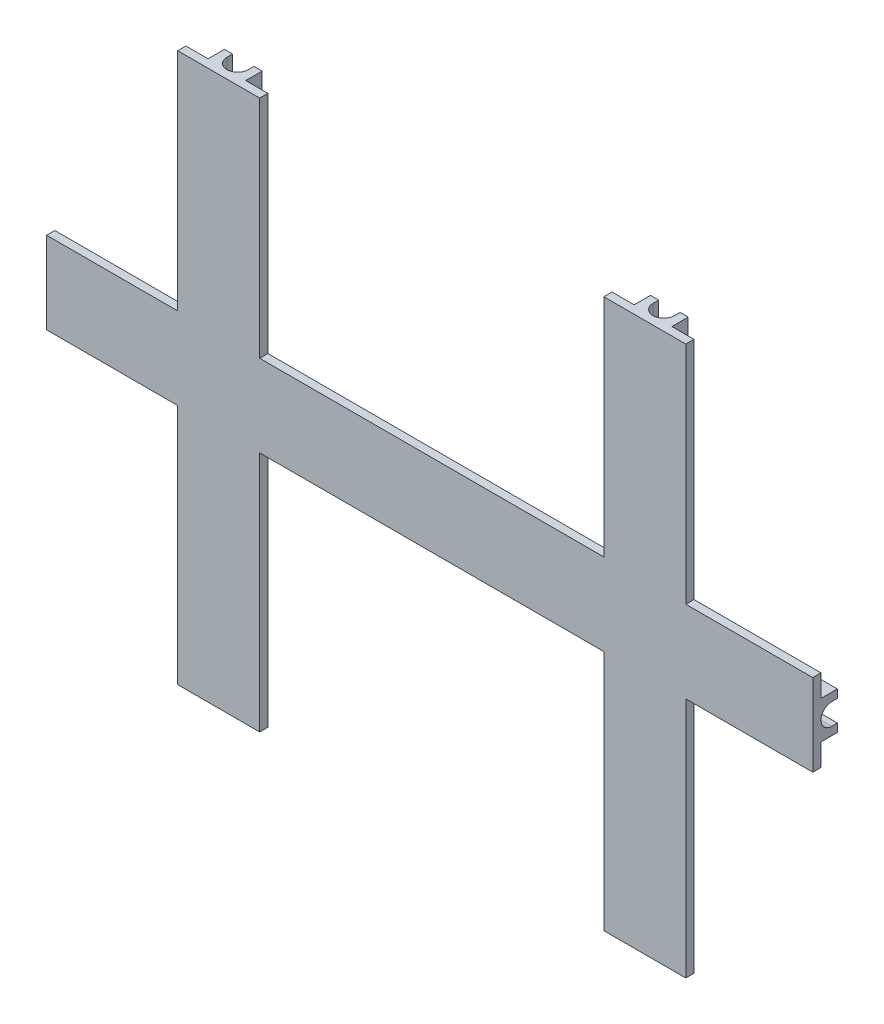
SolidWorks part; units mm, degrees
ref_plane "Спереди" through (0, 0, 0) normal (0, 0, 1) x (1, 0, 0)
ref_plane "Сверху" through (0, 0, 0) normal (0, 1, 0) x (1, 0, 0)
ref_plane "Справа" through (0, 0, 0) normal (1, 0, 0) x (0, 0, -1)
sketch "Skizze1" plane through (0, 0, 0) normal (0, 0, 1) x (1, 0, 0)
  line L0 (-31, -15.1875) -> (-31, 32.5)
  line L1 (-31, 32.5) -> (-21, 32.5)
  line L2 (-21, 32.5) -> (-21, 5)
  line L3 (-21, 5) -> (21, 5)
  line L4 (21, 5) -> (21, 32.5)
  line L5 (21, 32.5) -> (31, 32.5)
  line L6 (31, 32.5) -> (31, -34.5)
  line L7 (31, -34.5) -> (21, -34.5)
  line L8 (21, -34.5) -> (21, -5)
  line L9 (21, -5) -> (-21, -5)
  line L10 (-21, -5) -> (-21, -34.5)
  line L11 (-21, -34.5) -> (-31, -34.5)
  line L12 (-31, -34.5) -> (-31, -15.1875)
  dimension "D1" = 42
  dimension "D2" = 10
  dimension "D3" = 10
  dimension "D4" = 10
  dimension "D5" = 10
  dimension "D6" = 10
  dimension "D7" = 5
  dimension "D8" = 67
  dimension "D9" = 32.5
  dimension "D10" = 31
extrude "Aufsatz-Linear austragen1" add sketch "Skizze1" along normal blind 1
sketch "Skizze2" plane through (0, 0, 0) normal (0, 0, -1) x (-1, 0, 0)
  line L0 (31, 32.5) -> (31, -34.5) construction
  line L1 (31, 5) -> (47, 5)
  line L2 (31, 5) -> (31, -5)
  line L3 (31, -5) -> (47, -5)
  line L4 (47, 5) -> (47, -5)
  line L5 (-31, -34.5) -> (-31, 32.5) construction
  line L6 (-31, 5) -> (-46.5, 5)
  line L7 (-31, 5) -> (-31, -5)
  line L8 (-31, -5) -> (-46.5, -5)
  line L9 (-46.5, 5) -> (-46.5, -5)
  line L10 (-21, 5) -> (21, 5) construction
  dimension "D1" = 10
  dimension "D2" = 10
  dimension "D3" = 15.5
  dimension "D4" = 16
extrude "Aufsatz-Linear austragen2" add sketch "Skizze2" against normal blind 1
sketch "Skizze4" plane through (0, 0, 0) normal (0, 0, -1) x (-1, 0, 0)
  line L0 (-46.5, 5) -> (-46.5, -5) construction
  line L1 (-46.5, 2.3) -> (47, 2.3)
  line L2 (-46.5, 2.3) -> (-46.5, 1.3)
  line L3 (-46.5, 1.3) -> (47, 1.3)
  line L4 (47, 2.3) -> (47, 1.3)
  line L5 (47, -5) -> (47, 5) construction
  line L6 (-31, 32.5) -> (-21, 32.5) construction
  line L7 (-46.5, -1.3) -> (47, -1.3)
  line L8 (-46.5, -1.3) -> (-46.5, -2.3)
  line L9 (-46.5, -2.3) -> (47, -2.3)
  line L10 (47, -1.3) -> (47, -2.3)
  line L11 (-28.3, 32.5) -> (-27.3, 32.5)
  line L12 (-28.3, 32.5) -> (-28.3, -34.5)
  line L13 (-28.3, -34.5) -> (-27.3, -34.5)
  line L14 (-27.3, 32.5) -> (-27.3, -34.5)
  line L15 (-21, -34.5) -> (-31, -34.5) construction
  line L16 (31, -34.5) -> (21, -34.5) construction
  line L17 (-24.7, 32.5) -> (-23.7, 32.5)
  line L18 (-24.7, 32.5) -> (-24.7, -34.5)
  line L19 (-24.7, -34.5) -> (-23.7, -34.5)
  line L20 (-23.7, 32.5) -> (-23.7, -34.5)
  line L21 (23.7, -34.5) -> (24.7, -34.5)
  line L22 (23.7, -34.5) -> (23.7, 32.5)
  line L23 (23.7, 32.5) -> (24.7, 32.5)
  line L24 (24.7, -34.5) -> (24.7, 32.5)
  line L25 (21, 32.5) -> (31, 32.5) construction
  line L26 (-31, 5) -> (-31, 32.5) construction
  line L27 (27.3, 32.5) -> (28.3, 32.5)
  line L28 (27.3, 32.5) -> (27.3, -34.5)
  line L29 (27.3, -34.5) -> (28.3, -34.5)
  line L30 (28.3, 32.5) -> (28.3, -34.5)
  line L31 (-21, 32.5) -> (-21, 5) construction
  line L32 (21, 5) -> (21, 32.5) construction
  line L33 (31, 32.5) -> (31, 5) construction
  line L34 (47, 5) -> (31, 5) construction
  line L35 (31, -5) -> (47, -5) construction
  dimension "D1" = 2.7
  dimension "D2" = 1
  dimension "D3" = 1
  dimension "D4" = 2.7
  dimension "D5" = 1
  dimension "D6" = 2.7
  dimension "D7" = 1
  dimension "D8" = 2.7
  dimension "D9" = 1
  dimension "D10" = 2.7
  dimension "D11" = 1
  dimension "D12" = 2.7
extrude "Aufsatz-Linear austragen5" add sketch "Skizze4" along normal blind 2 contours L28 L29 L30 L27 | L24 L23 L22 L21 | L1 L4 L3 L2 | L7 L10 L9 L8 | L20 L19 L18 L17 | L14 L13 L12 L11
fillet "Verrundung1" radius 1.3 1 edges at (24.7, 17.4, 0)
fillet "Verrundung2" radius 1.3 1 edges at (27.3, 17.4, 0)
fillet "Verrundung3" radius 1.3 5 edges at (-37.65, 1.3, 0) (-26, 1.3, 0) (0, 1.3, 0) (26, 1.3, 0) (37.4, 1.3, 0)
fillet "Verrundung4" radius 1.3 5 edges at (37.4, -1.3, 0) (26, -1.3, 0) (0, -1.3, 0) (-26, -1.3, 0) (-37.65, -1.3, 0)
fillet "Verrundung5" radius 1.3 4 edges at (24.7, 2.3, -1.65) (27.3, 2.3, -1.65) (26.9192, 2.3, -0.3808) (25.0808, 2.3, -0.3808)
fillet "Verrundung6" radius 1.3 8 edges at (24.7, 1.3, -1.65) (24.7, -1.3, -1.65) (28.3, 1.3, -1.65) (28.3, -1.3, -1.65) (24.7, -0.9192, -0.3808) (24.7, 0.9192, -0.3808) (28.3, 0.9192, -0.3808) (28.3, -0.9192, -0.3808)
fillet "Verrundung7" radius 1.3 8 edges at (23.7, -1.3, -1.65) (23.7, 1.3, -1.65) (27.3, -1.3, -1.65) (27.3, 1.3, -1.65) (23.7, 0.9192, -0.3808) (23.7, -0.9192, -0.3808) (27.3, -0.9192, -0.3808) (27.3, 0.9192, -0.3808)
fillet "Verrundung8" radius 1.3 2 edges at (27.3, -18.4, 0) (24.7, -18.4, 0)
fillet "Verrundung9" radius 1.3 4 edges at (27.3, -2.3, -1.65) (24.7, -2.3, -1.65) (25.0808, -2.3, -0.3808) (26.9192, -2.3, -0.3808)
fillet "Verrundung10" radius 1.3 10 edges at (-24.7, -1.3, -1.65) (-24.7, -0.9192, -0.3808) (-24.7, 1.3, -1.65) (-28.3, -1.3, -1.65) (-28.3, 1.3, -1.65) (-24.7, 0.9192, -0.3808) (-24.7, -18.4, 0) (-24.7, 17.4, 0) (-28.3, -0.9192, -0.3808) (-28.3, 0.9192, -0.3808)
fillet "Verrundung11" radius 1.3 10 edges at (-23.7, 1.3, -1.65) (-23.7, -1.3, -1.65) (-27.3, 1.3, -1.65) (-27.3, -1.3, -1.65) (-27.3, -18.4, 0) (-23.7, -0.9192, -0.3808) (-23.7, 0.9192, -0.3808) (-27.3, -0.9192, -0.3808) (-27.3, 0.9192, -0.3808) (-27.3, 17.4, 0)
fillet "Verrundung12" radius 1.3 4 edges at (-24.7, -2.3, -1.65) (-27.3, -2.3, -1.65) (-25.0808, -2.3, -0.3808) (-26.9192, -2.3, -0.3808)
fillet "Verrundung13" radius 1.3 4 edges at (-27.3, 2.3, -1.65) (-24.7, 2.3, -1.65) (-25.0808, 2.3, -0.3808) (-26.9192, 2.3, -0.3808)
